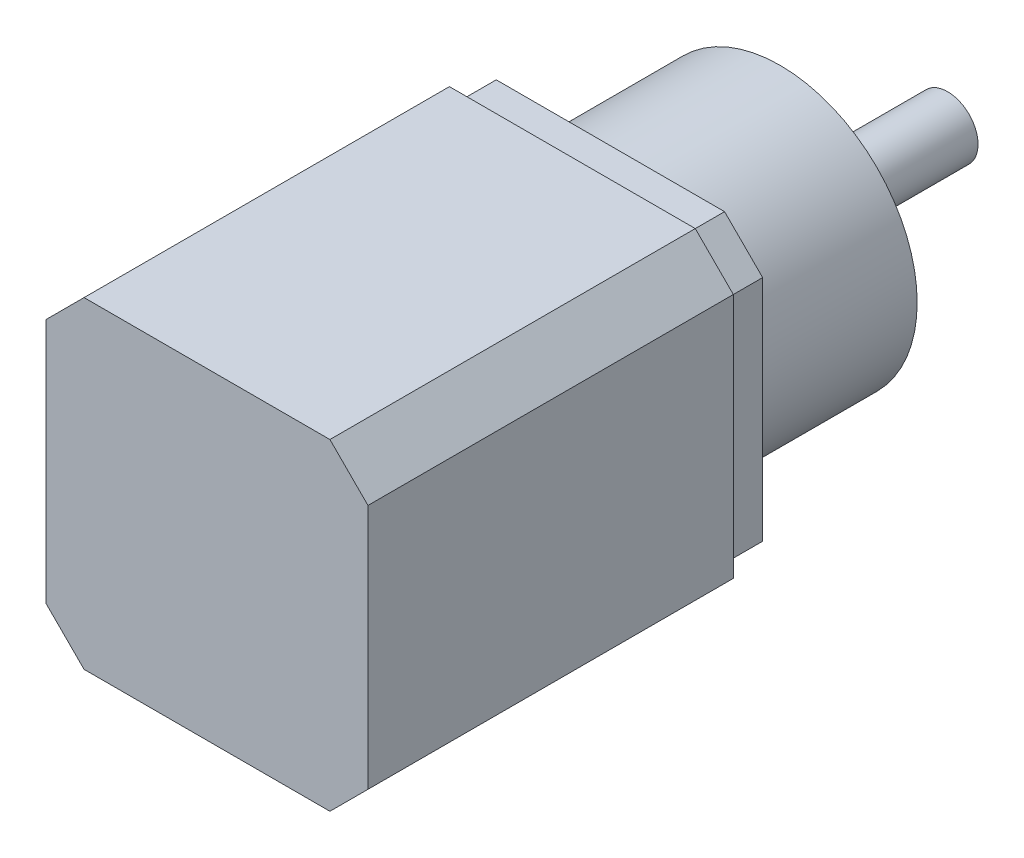
SolidWorks part; units mm, degrees
ref_plane "Front Plane" through (0, 0, 0) normal (0, 0, 1) x (1, 0, 0)
ref_plane "Top Plane" through (0, 0, 0) normal (0, 1, 0) x (1, 0, 0)
ref_plane "Right Plane" through (0, 0, 0) normal (1, 0, 0) x (0, 0, -1)
sketch "Sketch1" plane through (0, 0, 0) normal (0, 0, 1) x (1, 0, 0)
  line L1 (-21.15, 21.15) -> (21.15, 21.15)
  line L2 (-21.15, 21.15) -> (-21.15, -21.15)
  line L3 (-21.15, -21.15) -> (21.15, -21.15)
  line L4 (21.15, 21.15) -> (21.15, -21.15)
  line L5 (-21.15, 21.15) -> (21.15, -21.15) construction
  line L6 (-21.15, -21.15) -> (21.15, 21.15) construction
  point P0 (0, 0)
  dimension "D1" = 42.3
  dimension "D2" = 42.3
extrude "Boss-Extrude1" add sketch "Sketch1" along normal blind 48
chamfer "Chamfer1" distance 5 angle 45 4 edges at (-21.15, -21.15, 24) (21.15, -21.15, 24) (-21.15, 21.15, 24) (21.15, 21.15, 24)
sketch "Sketch2" plane through (0, 0, 0) normal (0, 0, -1) x (-1, 0, 0)
  line L1 (-20, -20) -> (20, -20)
  line L2 (-20, -20) -> (-20, 20)
  line L3 (-20, 20) -> (20, 20)
  line L4 (20, -20) -> (20, 20)
  line L5 (-20, -20) -> (20, 20) construction
  line L6 (-20, 20) -> (20, -20) construction
  point P0 (0, 0)
  dimension "D1" = 40
  dimension "D2" = 40
extrude "Boss-Extrude2" add sketch "Sketch2" along normal blind 5
chamfer "Chamfer2" distance 5 angle 45 4 edges at (20, -20, -2.5) (-20, -20, -2.5) (20, 20, -2.5) (-20, 20, -2.5)
sketch "Sketch3" plane through (0, 0, -5) normal (0, 0, -1) x (-1, 0, 0)
  circle A0 centre (0, 0) radius 18
  dimension "D1" = 36
extrude "Boss-Extrude3" add sketch "Sketch3" along normal blind 22.3
sketch "Sketch4" plane through (0, 0, -27.3) normal (0, 0, -1) x (-1, 0, 0)
  circle A0 centre (0, 0) radius 11
  dimension "D1" = 22
extrude "Boss-Extrude4" add sketch "Sketch4" along normal blind 2
sketch "Sketch5" plane through (0, 0, -29.3) normal (0, 0, -1) x (-1, 0, 0)
  circle A0 centre (0, 0) radius 4
  dimension "D1" = 8
extrude "Boss-Extrude5" add sketch "Sketch5" along normal blind 20
sketch "Sketch6" plane through (0, 0, -29.3) normal (0, 0, -1) x (-1, 0, 0)
  circle A0 centre (0, 0) radius 6.211
extrude "Boss-Extrude6" add sketch "Sketch6" along normal blind 0.5
sketch "Sketch7" plane through (0, 0, -27.3) normal (0, 0, -1) x (-1, 0, 0)
  line L0 (0, 0) -> (17.5, 17.5) construction
  line L1 (15, 20) -> (20, 15) construction
  circle A0 centre (0, 0) radius 14 construction
  circle A1 centre (9.8995, 9.8995) radius 1.25
  circle A2 centre (9.8995, -9.8995) radius 1.25
  circle A3 centre (-9.8995, -9.8995) radius 1.25
  circle A4 centre (-9.8995, 9.8995) radius 1.25
  point P17 (0, 0)
  dimension "D1" = 28
  dimension "D2" = 2.5
  dimension "D3" = 4
extrude "Cut-Extrude1" cut sketch "Sketch7" against normal blind 5
sketch "Sketch8" plane through (0, 0, -49.3) normal (0, 0, -1) x (-1, 0, 0)
  line L0 (-4, 4.1143) -> (-4, -4.5747) construction
  line L1 (3, 4.1143) -> (7.2799, 4.1143)
  line L2 (3, 4.1143) -> (3, -4.5747)
  line L3 (3, -4.5747) -> (7.2799, -4.5747)
  line L4 (7.2799, 4.1143) -> (7.2799, -4.5747)
  circle A0 centre (0, 0) radius 4 construction
  dimension "D1" = 7
extrude "Cut-Extrude2" cut sketch "Sketch8" against normal blind 15
